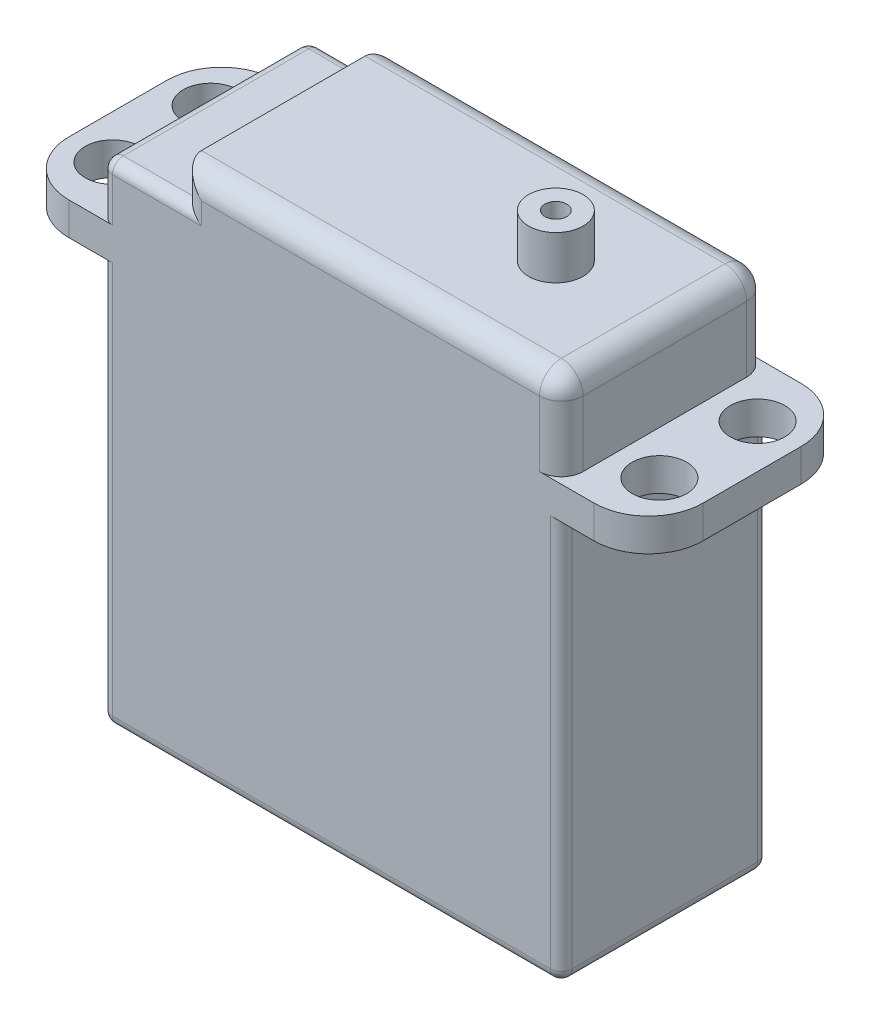
SolidWorks part; units mm, degrees
material "Gray Cast Iron"
ref_plane "Front" through (0, 0, 0) normal (0, 0, 1) x (1, 0, 0)
ref_plane "Top" through (0, 0, 0) normal (0, 1, 0) x (1, 0, 0)
ref_plane "Right" through (0, 0, 0) normal (1, 0, 0) x (0, 0, -1)
sketch "Sketch1" plane through (0, 0, 0) normal (0, 0, 1) x (1, 0, 0)
  line L1 (-17.3428, 2.3164) -> (24.8195, 2.3164)
  line L2 (-17.3428, 2.3164) -> (-17.3428, 39.3164)
  line L3 (-17.3428, 39.3164) -> (24.8195, 39.3164)
  line L4 (24.8195, 2.3164) -> (24.8195, 39.3164)
  line L5 (-25.3428, 42.3164) -> (32.8195, 42.3164)
  line L6 (-25.3428, 42.3164) -> (-25.3428, 39.3164)
  line L7 (-25.3428, 39.3164) -> (32.8195, 39.3164)
  line L8 (32.8195, 42.3164) -> (32.8195, 39.3164)
  line L9 (-10.1805, 47.3164) -> (24.8195, 47.3164)
  line L10 (-10.1805, 47.3164) -> (-10.1805, 50.3164)
  line L11 (-17.3428, 42.3164) -> (24.8195, 42.3164)
  line L12 (-17.3428, 42.3164) -> (-17.3428, 47.3164)
  line L13 (-17.3428, 47.3164) -> (24.8195, 47.3164)
  line L14 (24.8195, 42.3164) -> (24.8195, 47.3164)
  line L15 (-10.1805, 50.3164) -> (24.8195, 50.3164)
  line L16 (24.8195, 47.3164) -> (24.8195, 50.3164)
  point P4 (3.7383, 40.1582)
  dimension "D1" = 37
  dimension "D2" = 3
  dimension "D3" = 8
  dimension "D4" = 8
  dimension "D5" = 5
  dimension "D6" = 3
  dimension "D7" = 35
extrude "Boss-Extrude1" add sketch "Sketch1" along normal blind 19 contours L1 L4 L3 L2 | L8 L5 L6 L7 L3 | L5 L14 L9 L13 L12 | L9 L16 L15 L10 region at (3.7383, 20.8164, 0) region at (3.7383, 40.8164, 0) region at (3.7383, 44.8164, 0) region at (7.3195, 48.8164, 0)
sketch "Sketch2" plane through (0, 42.3164, 0) normal (0, 1, 0) x (1, 0, 0)
  line L0 (-25.3428, 0) -> (-17.3428, 0) construction
  line L1 (-17.3428, -19) -> (-17.3428, 0) construction
  line L2 (-25.3428, -19) -> (-17.3428, -19) construction
  line L3 (24.8195, -19) -> (24.8195, 0) construction
  line L4 (24.8195, -19) -> (24.8195, 0) construction
  line L5 (24.8195, 0) -> (32.8195, 0) construction
  line L6 (24.8195, -19) -> (32.8195, -19) construction
  circle A0 centre (-21.3428, -14) radius 2.5
  circle A1 centre (-21.3428, -5) radius 2.5
  circle A2 centre (28.8195, -5) radius 2.5
  circle A3 centre (28.8195, -14) radius 2.5
  dimension "D2" = 5
  dimension "D3" = 4
  dimension "D1" = 5
  dimension "D4" = 4
  dimension "D5" = 5
  dimension "D6" = 4
  dimension "D7" = 4
  dimension "D8" = 5
  dimension "D9" = 5
extrude "Cut-Extrude1" cut sketch "Sketch2" against normal blind 19
sketch "Sketch4" plane through (0, 50.3164, 0) normal (0, 1, 0) x (1, 0, 0)
  line L0 (-10.1805, -19) -> (24.8195, -19) construction
  line L1 (24.8195, -19) -> (24.8195, 0) construction
  circle A0 centre (14.8195, -9.5) radius 2.5
  circle A1 centre (14.8195, -9.5) radius 1
  dimension "D1" = 2
  dimension "D2" = 5
  dimension "D3" = 9.5
  dimension "D4" = 10
extrude "Boss-Extrude2" add sketch "Sketch4" along normal blind 4
fillet "Fillet1" radius 2 2 edges at (-10.1805, 48.8164, 0) (-10.1805, 48.8164, 19)
fillet "Fillet2" radius 2 5 edges at (8.3195, 50.3164, 0) (24.8195, 46.3164, 0) (8.3195, 50.3164, 19) (24.8195, 50.3164, 9.5) (24.8195, 46.3164, 19) tangent propagation no
fillet "Fillet3" radius 5 4 edges at (-25.3428, 40.8164, 0) (-25.3428, 40.8164, 19) (32.8195, 40.8164, 0) (32.8195, 40.8164, 19)
fillet "Fillet4" radius 1 5 edges at (-12.7617, 47.3164, 0) (-17.3428, 44.8164, 0) (-17.3428, 47.3164, 9.5) (-17.3428, 44.8164, 19) (-12.7617, 47.3164, 19)
fillet "Fillet5" radius 1 8 edges at (24.8195, 20.8164, 0) (24.8195, 2.3164, 9.5) (24.8195, 20.8164, 19) (3.7383, 2.3164, 19) (3.7383, 2.3164, 0) (-17.3428, 2.3164, 9.5) (-17.3428, 20.8164, 0) (-17.3428, 20.8164, 19)
